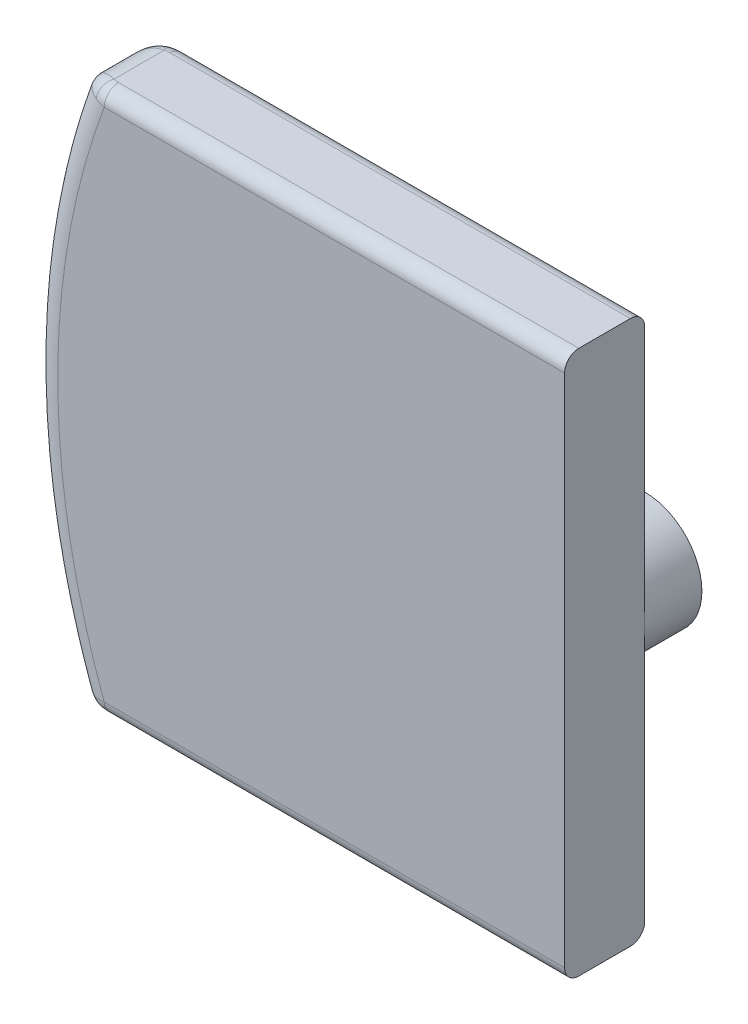
SolidWorks part; units mm, degrees
ref_plane "Front" through (0, 0, 0) normal (0, 0, 1) x (1, 0, 0)
ref_plane "Top" through (0, 0, 0) normal (0, 1, 0) x (1, 0, 0)
ref_plane "Right" through (0, 0, 0) normal (1, 0, 0) x (0, 0, -1)
sketch "Sketch1" plane through (0, 0, 0) normal (0, 0, 1) x (1, 0, 0)
  line L2 (0, -9.5) -> (16.9665, -9.5)
  line L3 (16.9665, -9.5) -> (16.9665, 9.5)
  line L4 (16.9665, 9.5) -> (0, 9.5)
  arc A1 (0, 9.5) -> (0, -9.5) centre (25, 0) ccw
extrude "Boss-Extrude2" add sketch "Sketch1" along normal blind 2.8
fillet "Fillet3" radius 1 4 edges at (0, 9.5, 1.4) (-1.7442, 0, 2.8) (0, -9.5, 1.4) (-1.7442, 0, 0)
fillet "Fillet4" radius 0.5 12 edges at (0.071, -9.2778, 2.3181) (0.071, -9.2778, 0.4819) (0.071, 9.2778, 0.4819) (0.071, 9.2778, 2.3181) (9.0196, -9.5, 2.8) (9.0196, -9.5, 0) (9.0196, 9.5, 0) (9.0196, 9.5, 2.8)
sketch "Sketch4" plane through (0, 0, 0) normal (0, 0, -1) x (-1, 0, 0)
  line L3 (-4, 0) -> (-4, 3)
  line L4 (-4, 3) -> (-4.1, 3)
  line L5 (-4, 0) -> (-4, -3)
  line L6 (-4, -3) -> (-4.1, -3)
  line L7 (-4.1, -3) -> (-4.1, 3)
  line L9 (-8.1051, 0) -> (-8.1051, 3)
  line L10 (-8.1051, 0) -> (-8.1051, -3)
  line L11 (-8.1051, -3) -> (-8.2051, -3)
  line L12 (-8.2051, -3) -> (-8.2051, 3)
  line L13 (-8.2051, 3) -> (-8.1051, 3)
  line L14 (-9.1109, 3.9767) -> (-7.2254, 3.9767)
  line L15 (-7.2254, 3.9767) -> (-7.2254, 4.7729)
  line L16 (-7.2254, 4.7729) -> (-7.3349, 4.7729)
  line L17 (-7.3349, 4.7729) -> (-7.3349, 4.0725)
  line L18 (-7.3349, 4.0725) -> (-9.1109, 4.0725)
  line L19 (-9.1109, 4.0725) -> (-9.1109, 3.9767)
  line L20 (-5.108, 3.9767) -> (-5.108, 4.0725)
  line L21 (-5.108, 4.0725) -> (-3.704, 4.0725)
  line L22 (-3.704, 4.0725) -> (-3.704, 4.7729)
  line L23 (-3.704, 4.7729) -> (-5.108, 4.7729)
  line L24 (-5.108, 4.7729) -> (-5.108, 4.8683)
  line L25 (-5.108, 4.8683) -> (-3.6176, 4.8683)
  line L26 (-3.6176, 4.8683) -> (-3.6176, 3.9767)
  line L27 (-3.6176, 3.9767) -> (-5.108, 3.9767)
extrude "Cut-Extrude2" cut sketch "Sketch4" against normal blind 0.2
sketch "Sketch8" plane through (0, 0, 0) normal (0, 0, -1) x (-1, 0, 0)
  circle A0 centre (-14.9665, 0) radius 2
extrude "Boss-Extrude4" add sketch "Sketch8" along normal blind 2
sketch "Sketch9" plane through (0, 0, -2) normal (0, 0, -1) x (-1, 0, 0)
  circle A0 centre (-14.9665, 0) radius 1.1
extrude "Cut-Extrude3" cut sketch "Sketch9" against normal blind 3.5
